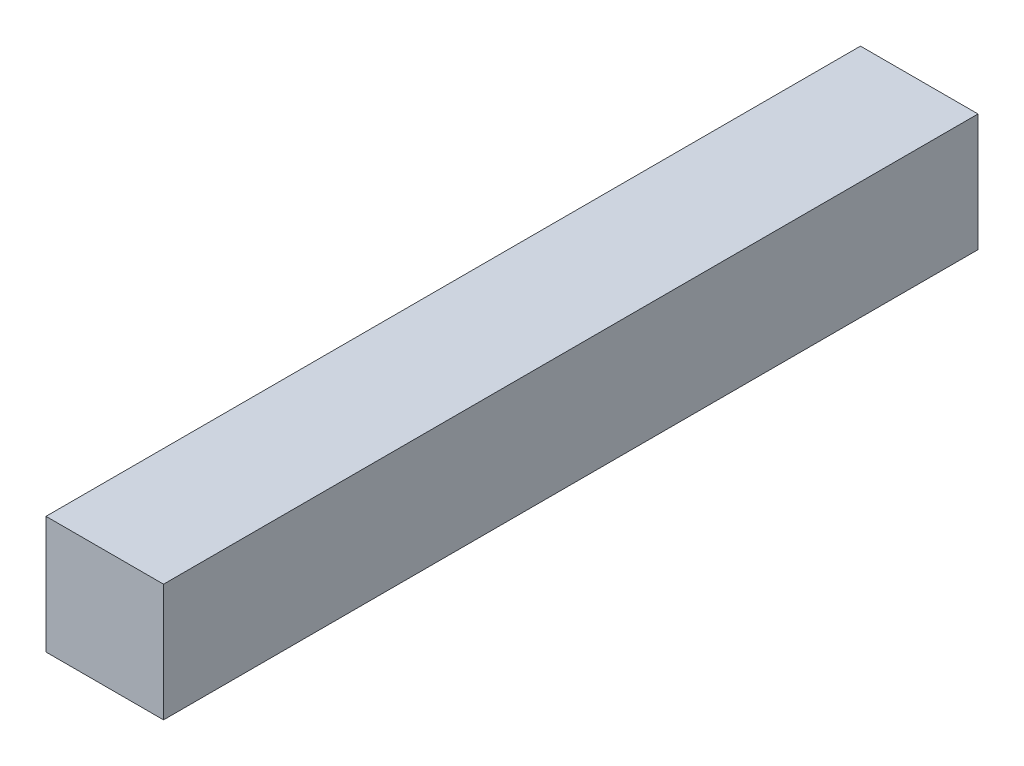
SolidWorks part; units mm, degrees
ref_plane "Front Plane" through (0, 0, 0) normal (0, 0, 1) x (1, 0, 0)
ref_plane "Top Plane" through (0, 0, 0) normal (0, 1, 0) x (1, 0, 0)
ref_plane "Right Plane" through (0, 0, 0) normal (1, 0, 0) x (0, 0, -1)
sketch "Sketch1" plane through (0, 0, 0) normal (0, 0, 1) x (1, 0, 0)
  line L1 (-3.175, -3.175) -> (3.175, -3.175)
  line L2 (-3.175, -3.175) -> (-3.175, 3.175)
  line L3 (-3.175, 3.175) -> (3.175, 3.175)
  line L4 (3.175, -3.175) -> (3.175, 3.175)
  line L5 (-3.175, -3.175) -> (3.175, 3.175) construction
  line L6 (-3.175, 3.175) -> (3.175, -3.175) construction
  point P0 (0, 0)
  dimension "D1" = 6.35
extrude "Boss-Extrude1" add sketch "Sketch1" along normal mid plane 44
ref_axis "Axis1" through (0, 0, -24.289) along (0, 0, 1)
